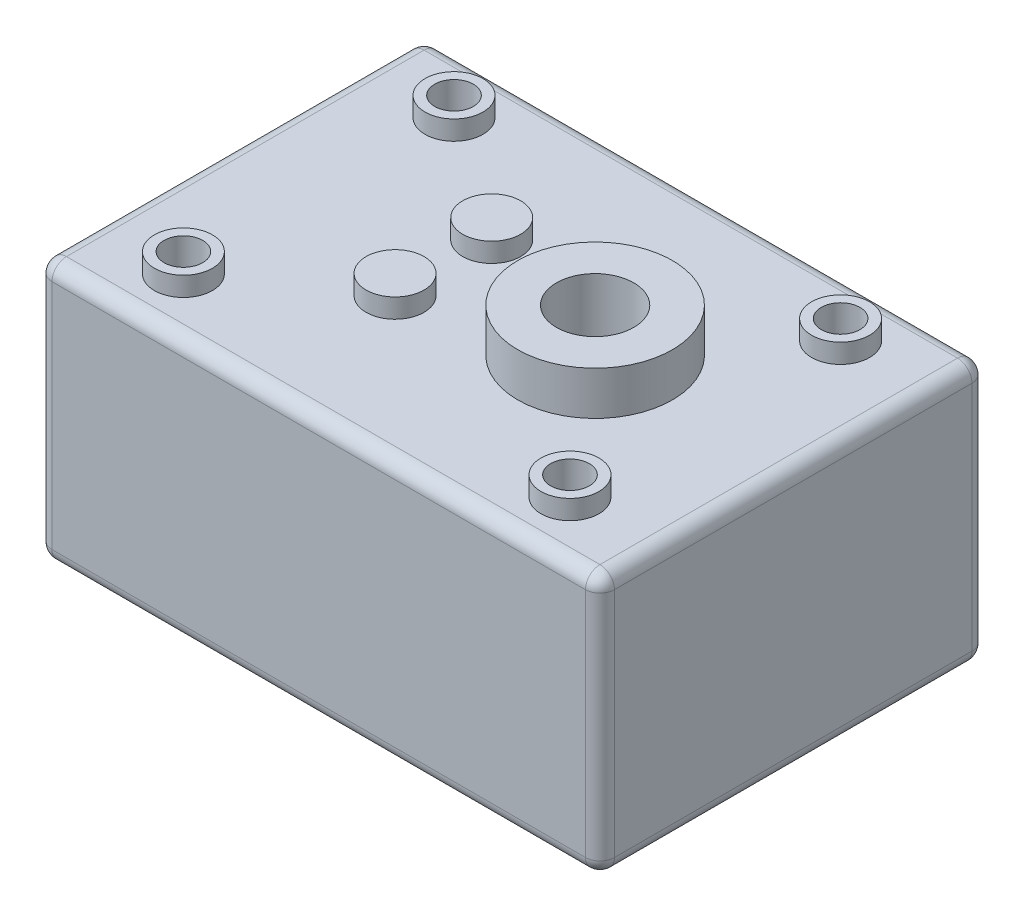
SolidWorks part; units mm, degrees
other "Markup1"
sketch "Sketch28" plane through (0, 31.5, -40) normal (0.0465, 0.1553, -0.9868) x (-0.9966, -0.0607, -0.0565)
sketch "Sketch29" plane through (0, 31.5, -40) normal (0.0465, 0.1553, -0.9868) x (-0.9966, -0.0607, -0.0565)
ref_plane "Front Plane" through (0, 0, 0) normal (0, 0, 1) x (1, 0, 0)
ref_plane "Top Plane" through (0, 0, 0) normal (0, 1, 0) x (1, 0, 0)
ref_plane "Right Plane" through (0, 0, 0) normal (1, 0, 0) x (0, 0, -1)
sketch "Sketch1" plane through (0, 0, 0) normal (0, 1, 0) x (1, 0, 0)
  line L1 (0, 0) -> (-58.2, 0)
  line L2 (0, 0) -> (0, 40)
  line L3 (0, 40) -> (-58.2, 40)
  line L4 (-58.2, 0) -> (-58.2, 40)
  dimension "D1" = 58.2
  dimension "D2" = 40
extrude "Boss-Extrude1" add sketch "Sketch1" along normal blind 27
sketch "Sketch2" plane through (0, 27, 0) normal (0, 1, 0) x (1, 0, 0)
  line L0 (-58.2, 40) -> (-58.2, 0) construction
  line L1 (0, 40) -> (-58.2, 40) construction
  circle A0 centre (-49.1, 34) radius 3
  dimension "D3" = 6
  dimension "D1" = 9.1
  dimension "D2" = 6
extrude "Boss-Extrude2" add sketch "Sketch2" along normal blind 2
sketch "Sketch3" plane through (0, 29, 0) normal (0, 1, 0) x (1, 0, 0)
  circle A0 centre (-49.1, 34) radius 2
  dimension "D1" = 4
extrude "Cut-Extrude1" cut sketch "Sketch3" against normal blind 31
sketch "Sketch4" plane through (0, 27, 0) normal (0, 1, 0) x (1, 0, 0)
  line L0 (0, 0) -> (0, 40) construction
  line L1 (0, 40) -> (-58.2, 40) construction
  circle A0 centre (-9.1, 34) radius 3
  dimension "D1" = 6
  dimension "D2" = 9.1
  dimension "D3" = 6
extrude "Boss-Extrude3" add sketch "Sketch4" along normal blind 2
sketch "Sketch5" plane through (0, 29, 0) normal (0, 1, 0) x (1, 0, 0)
  circle A0 centre (-9.1, 34) radius 2
  dimension "D1" = 4
extrude "Cut-Extrude2" cut sketch "Sketch5" against normal blind 31
sketch "Sketch6" plane through (0, 27, 0) normal (0, 1, 0) x (1, 0, 0)
  line L0 (-58.2, 0) -> (0, 0) construction
  line L1 (-58.2, 40) -> (-58.2, 0) construction
  circle A0 centre (-49.1, 6) radius 3
  dimension "D1" = 6
  dimension "D2" = 6
  dimension "D3" = 9.1
extrude "Boss-Extrude4" add sketch "Sketch6" along normal blind 2
sketch "Sketch7" plane through (0, 29, 0) normal (0, 1, 0) x (1, 0, 0)
  circle A0 centre (-49.1, 6) radius 2
  dimension "D1" = 4
extrude "Cut-Extrude3" cut sketch "Sketch7" against normal blind 31
sketch "Sketch8" plane through (0, 27, 0) normal (0, 1, 0) x (1, 0, 0)
  line L0 (0, 0) -> (0, 40) construction
  line L1 (-58.2, 0) -> (0, 0) construction
  circle A0 centre (-9.1, 6) radius 3
  dimension "D1" = 6
  dimension "D2" = 9.1
  dimension "D3" = 6
extrude "Boss-Extrude5" add sketch "Sketch8" along normal blind 2
sketch "Sketch9" plane through (0, 29, 0) normal (0, 1, 0) x (1, 0, 0)
  circle A0 centre (-9.1, 6) radius 2
  dimension "D1" = 4
extrude "Cut-Extrude4" cut sketch "Sketch9" against normal blind 31
sketch "Sketch10" plane through (0, 27, 0) normal (0, 1, 0) x (1, 0, 0)
  line L0 (0, 0) -> (0, 40) construction
  line L1 (0, 40) -> (-58.2, 40) construction
  circle A0 centre (-20.5, 20) radius 8
  dimension "D1" = 16
  dimension "D2" = 20.5
  dimension "D3" = 20
extrude "Boss-Extrude6" add sketch "Sketch10" along normal blind 4.5
sketch "Sketch11" plane through (0, 31.5, 0) normal (0, 1, 0) x (1, 0, 0)
  circle A0 centre (-20.5, 20) radius 4
  dimension "D1" = 8
extrude "Cut-Extrude5" cut sketch "Sketch11" against normal blind 36
sketch "Sketch12" plane through (0, 0, 0) normal (0, -1, 0) x (1, 0, 0)
  circle A0 centre (-49.1, -6) radius 3
  dimension "D1" = 6
extrude "Boss-Extrude7" add sketch "Sketch12" along normal blind 2
sketch "Sketch13" plane through (0, 0, 0) normal (0, -1, 0) x (1, 0, 0)
  circle A0 centre (-49.1, -34) radius 3
  circle A1 centre (-9.1, -6) radius 3
  circle A2 centre (-9.1, -34) radius 3
  dimension "D1" = 6
  dimension "D2" = 6
  dimension "D3" = 6
extrude "Boss-Extrude8" add sketch "Sketch13" along normal blind 2
sketch "Sketch15" plane through (0, 0, 0) normal (0, -1, 0) x (1, 0, 0)
  circle A0 centre (-20.5, -20) radius 8
  dimension "D1" = 16
extrude "Boss-Extrude9" add sketch "Sketch15" along normal blind 4.5
sketch "Sketch18" plane through (0, 0, 0) normal (0, 1, 0) x (1, 0, 0)
  circle A0 centre (-9.1, 6) radius 2
  dimension "D1" = 4
extrude "Cut-Extrude11" cut sketch "Sketch18" against normal through all
sketch "Sketch19" plane through (0, 0, 0) normal (0, 1, 0) x (1, 0, 0)
  circle A0 centre (-20.5, 20) radius 4
  dimension "D1" = 8
extrude "Cut-Extrude12" cut sketch "Sketch19" against normal through all
sketch "Sketch20" plane through (0, 0, 0) normal (0, 1, 0) x (1, 0, 0)
  circle A0 centre (-49.1, 34) radius 2
  circle A1 centre (-49.1, 6) radius 2
  circle A2 centre (-9.1, 34) radius 2
  dimension "D1" = 4
  dimension "D2" = 4
  dimension "D3" = 4
extrude "Cut-Extrude13" cut sketch "Sketch20" against normal through all
sketch "Sketch24" plane through (0, 27, 0) normal (0, 1, 0) x (1, 0, 0)
  line L0 (-58.2, 40) -> (-58.2, 0) construction
  line L2 (-58.2, 0) -> (0, 0) construction
  circle A0 centre (-36.2, 15) radius 3
  dimension "D1" = 6
  dimension "D2" = 22
  dimension "D3" = 15
extrude "Boss-Extrude11" add sketch "Sketch24" along normal blind 2
sketch "Sketch25" plane through (0, 27, 0) normal (0, 1, 0) x (1, 0, 0)
  line L0 (0, 40) -> (-58.2, 40) construction
  line L1 (-58.2, 40) -> (-58.2, 0) construction
  circle A0 centre (-36.2, 25) radius 3
  dimension "D1" = 6
  dimension "D2" = 15
  dimension "D3" = 22
extrude "Boss-Extrude12" add sketch "Sketch25" along normal blind 2
sketch "Sketch26" plane through (0, 0, 0) normal (0, -1, 0) x (1, 0, 0)
  line L0 (-58.2, -40) -> (-58.2, 0) construction
  line L1 (-58.2, 0) -> (0, 0) construction
  circle A0 centre (-36.2, -15) radius 3
  dimension "D1" = 6
  dimension "D2" = 22
  dimension "D3" = 15
extrude "Boss-Extrude13" add sketch "Sketch26" along normal blind 2
sketch "Sketch27" plane through (0, 0, 0) normal (0, -1, 0) x (1, 0, 0)
  line L0 (0, -40) -> (-58.2, -40) construction
  circle A0 centre (-36.2, -25) radius 3
  dimension "D1" = 6
  dimension "D2" = 15
extrude "Boss-Extrude14" add sketch "Sketch27" along normal blind 2
fillet "Fillet5" radius 1.5 11 edges at (-58.2, 27, -20) (-58.2, 13.5, 0) (-58.2, 0, -20) (-29.1, 0, -40) (-58.2, 13.5, -40) (-29.1, 27, -40) (-29.1, 0, 0) (0, 0, -20) (0, 13.5, 0) (0, 27, -20) (-29.1, 27, 0)
fillet "Fillet6" radius 1.5 3 edges at (-0.4393, 26.5607, -39.5607) (-0.4393, 0.4393, -39.5607) (0, 13.5, -40)
